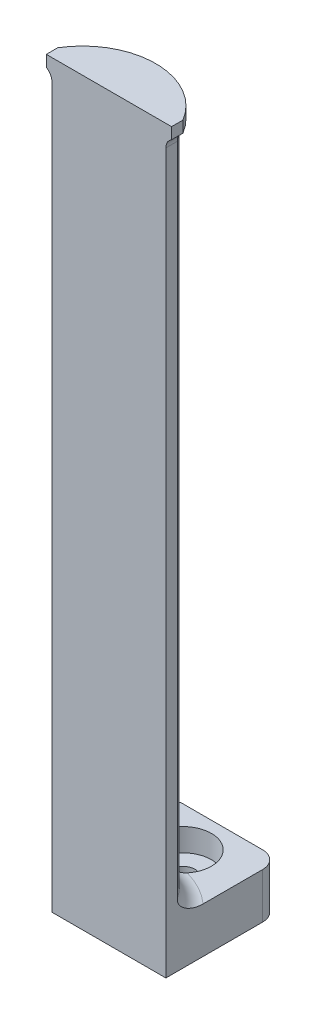
SolidWorks part; units mm, degrees
ref_plane "Plan de face" through (0, 0, 0) normal (0, 0, 1) x (1, 0, 0)
ref_plane "Plan de dessus" through (0, 0, 0) normal (0, 1, 0) x (1, 0, 0)
ref_plane "Plan de droite" through (0, 0, 0) normal (1, 0, 0) x (0, 0, -1)
sketch "Esquisse2" plane through (0, 0, 0) normal (0, 1, 0) x (1, 0, 0)
  line L0 (-10, 0) -> (10, 0)
  arc A0 (-10, 0) -> (10, 0) centre (0, -6.6332) cw
  dimension "D3" = 12
  dimension "D1" = 20
  dimension "D2" = 10
extrude "Boss.-Extru.1" add sketch "Esquisse2" along normal blind 120
sketch "Esquisse3" plane through (0, 0, 0) normal (0, -1, 0) x (1, 0, 0)
  line L1 (10, 0) -> (-10, 0)
  line L2 (10, 0) -> (10, -18)
  line L3 (10, -18) -> (-10, -18)
  line L4 (-10, 0) -> (-10, -18)
  dimension "D1" = 18
extrude "Boss.-Extru.2" add sketch "Esquisse3" along normal blind 8
fillet "Congé1" radius 3 1 edges at (0, 0, -5.3668)
fillet "Congé2" radius 3 2 edges at (-10, -4, -18) (10, -4, -18)
sketch "Esquisse4" plane through (0, 0, 0) normal (0, 1, 0) x (1, 0, 0)
  line L0 (-10, 4.5471) -> (-10, 15) construction
  line L1 (-7, 18) -> (7, 18) construction
  circle A0 centre (0, 11) radius 2.1
  dimension "D3" = 4.2
  dimension "D1" = 10
  dimension "D2" = 7
extrude "Enlèv. mat.-Extru.1" cut sketch "Esquisse4" against normal through all and the other way through all
sketch "Esquisse5" plane through (0, 0, 0) normal (0, 1, 0) x (1, 0, 0)
  circle A0 centre (0, 11) radius 5
  dimension "D1" = 10
extrude "Enlèv. mat.-Extru.2" cut sketch "Esquisse5" along normal through all and the other way blind 4
sketch "Esquisse7" plane through (0, 0, 0) normal (0, 0, 1) x (1, 0, 0)
  line L1 (-10, 120) -> (10, 120)
  line L2 (-10, 120) -> (-10, -8)
  line L3 (-10, -8) -> (10, -8)
  line L4 (10, 120) -> (10, -8)
extrude "Boss.-Extru.3" add sketch "Esquisse7" along normal blind 2
sketch "Esquisse8" plane through (0, 120, 0) normal (0, 1, 0) x (1, 0, 0)
  line L0 (-11, -2) -> (11, -2)
  line L1 (11, -2) -> (11, 0)
  line L3 (-11, 0) -> (-11, -2)
  arc A0 (10, 0) -> (-10, 0) centre (0, -6.6332) ccw construction
  arc A1 (-11, 0) -> (11, 0) centre (0, -6.6332) cw
  dimension "D1" = 22
  dimension "D2" = 1
  dimension "D3" = 2
  dimension "D4" = 1
extrude "Boss.-Extru.4" add sketch "Esquisse8" along normal blind 2
fillet "Congé3" radius 2 3 edges at (0, 120, -5.3668)
